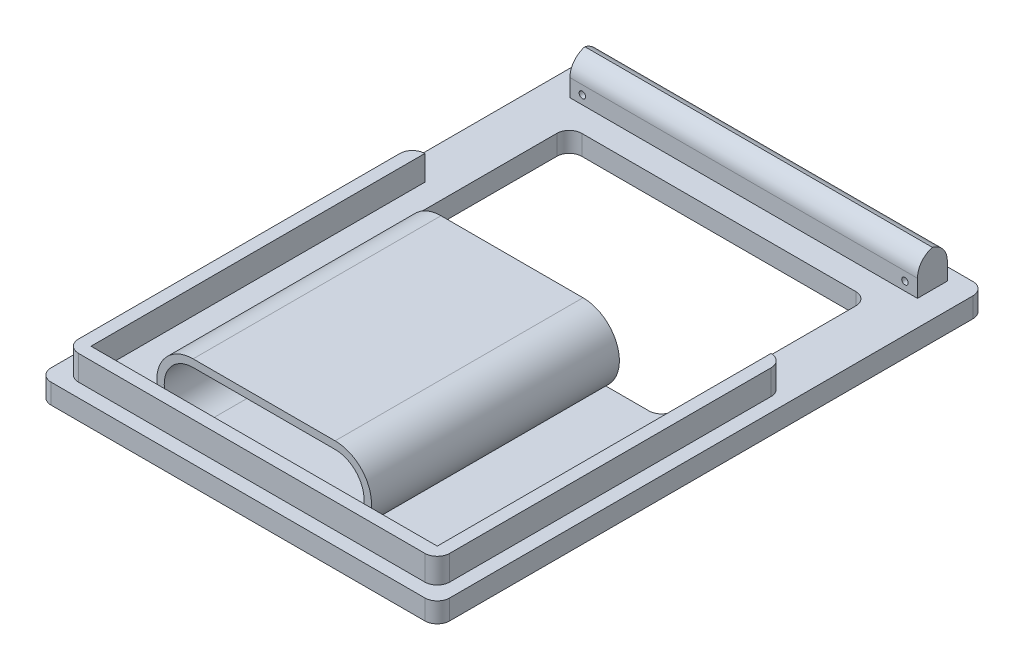
SolidWorks part; units mm, degrees
ref_plane "Front Plane" through (0, 0, 0) normal (0, 0, 1) x (1, 0, 0)
ref_plane "Top Plane" through (0, 0, 0) normal (0, 1, 0) x (1, 0, 0)
ref_plane "Right Plane" through (0, 0, 0) normal (1, 0, 0) x (0, 0, -1)
sketch "Sketch3" plane through (0, 0, 0) normal (0, 1, 0) x (1, 0, 0)
  line L0 (-75, 110) -> (75, 110)
  line L1 (-75, -105) -> (75, -105)
  line L2 (-75, -105) -> (-75, 105)
  line L4 (75, -105) -> (75, 105)
  line L5 (-75, -105) -> (75, 105) construction
  line L6 (-75, 105) -> (75, -105) construction
  line L7 (80, -105) -> (80, 105)
  line L8 (-75, -110) -> (75, -110)
  line L9 (-80, -105) -> (-80, 105)
  line L10 (-80, -110) -> (80, -110) construction
  line L11 (-80, -110) -> (-80, 110) construction
  line L12 (80, -110) -> (80, 110) construction
  line L13 (-80, 110) -> (80, 110) construction
  line L15 (-75, 105) -> (75, 105)
  line L19 (-75, 105) -> (75, 105) construction
  line L20 (-69.75, 105) -> (69.75, 105)
  line L21 (-69.75, 105) -> (-69.75, 93)
  line L22 (-69.75, 93) -> (69.75, 93)
  line L23 (69.75, 105) -> (69.75, 93)
  arc A0 (-75, -110) -> (-80, -105) centre (-75, -105) cw
  arc A1 (80, -105) -> (75, -110) centre (75, -105) cw
  arc A2 (75, 110) -> (80, 105) centre (75, 105) cw
  arc A3 (-75, 110) -> (-80, 105) centre (-75, 105) ccw
  point P0 (0, 0)
  point P5 (0, 93)
  dimension "D4" = 5
  dimension "D1" = 75
  dimension "D2" = 210
  dimension "D5" = 12
  dimension "D6" = 139.5
  dimension "D3" = 5
extrude "Boss-Extrude1" add sketch "Sketch3" along normal blind 8 contours L1 L4 L2 | L0 A3 L9 A0 L8 A1 L7 A2 L4 L1 L2 | L2 L4 | L23 L15 L21 L22 region at (0, 0, -107.2797) region at (0, 0, 5.5564) region at (0, 0, -99)
extrude "Boss-Extrude2" add sketch "Sketch3<7>" along normal blind 15 from surface contours L23 L15 L21 L22 region at (0, 0, -99) starting at face at (0, 8, 0)
sketch "Sketch3<7>" plane through (0, 0, 0) normal (0, 1, 0) x (1, 0, 0) same geometry as "Sketch3"
fillet "Fillet1" radius 8 2 edges at (0, 23, -93) (0, 23, -105)
sketch "Sketch4" plane through (0, 0, 0) normal (0, -1, 0) x (1, 0, 0)
  line L0 (69.75, -93) -> (-69.75, -93) construction
  line L1 (-55, 0) -> (55, 0)
  line L2 (-60, -5) -> (-60, -78)
  line L3 (-55, -83) -> (55, -83)
  line L4 (60, -5) -> (60, -78)
  line L5 (-75, 110) -> (75, 110) construction
  line L6 (80, 105) -> (80, -105) construction
  arc A0 (-55, 0) -> (-60, -5) centre (-55, -5) ccw
  arc A1 (-60, -78) -> (-55, -83) centre (-55, -78) ccw
  arc A2 (55, -83) -> (60, -78) centre (55, -78) ccw
  arc A3 (55, 0) -> (60, -5) centre (55, -5) cw
  point P4 (0, -83)
  point P12 (0, 0)
  dimension "D4" = 5
  dimension "D1" = 10
  dimension "D2" = 110
  dimension "D3" = 20
extrude "Cut-Extrude1" cut sketch "Sketch4" against normal up to next
sketch "Sketch5" plane through (0, 8, 0) normal (0, 1, 0) x (1, 0, 0)
  line L0 (75, -105) -> (75, 105) construction
  line L1 (-75, -105) -> (75, -105) construction
  line L2 (-75, -105) -> (-75, 105) construction
  line L3 (-75, 105) -> (75, 105) construction
  line L4 (75, 110) -> (-75, 110)
  line L5 (80, -105) -> (80, 105)
  line L6 (-75, -110) -> (75, -110)
  line L7 (-80, 105) -> (-80, -105)
  line L8 (75, 110) -> (-75, 110)
  line L9 (80, -105) -> (80, 105)
  line L10 (-75, -110) -> (75, -110)
  line L11 (-80, 105) -> (-80, -105)
  line L12 (69.75, 105) -> (-69.75, 105)
  line L13 (-69.75, 105) -> (-69.75, 93)
  line L14 (-69.75, 93) -> (69.75, 93)
  line L15 (69.75, 93) -> (69.75, 105)
  line L16 (69.75, 105) -> (-69.75, 105)
  line L17 (-69.75, 105) -> (-69.75, 93)
  line L18 (-69.75, 93) -> (69.75, 93)
  line L19 (69.75, 93) -> (69.75, 105)
  line L20 (75, -105) -> (75, 105)
  line L21 (-75, -105) -> (75, -105)
  line L22 (-75, -105) -> (-75, 105)
  line L23 (-75, 105) -> (75, 105)
  line L24 (-75, 35) -> (75, 35)
  line L25 (-69.5, 34.5) -> (-69.5, -99.5)
  line L26 (-69.5, -104.5) -> (69.5, -104.5)
  line L27 (-74.5, -99.5) -> (-74.5, 29.5)
  line L28 (-69.5, 34.5) -> (69.5, 34.5)
  line L29 (74.5, -99.5) -> (74.5, 29.5)
  line L30 (-69.5, -99.5) -> (69.5, -99.5)
  line L31 (69.5, -99.5) -> (69.5, 34.5)
  arc A0 (-74.5, 29.5) -> (-69.5, 34.5) centre (-69.5, 29.5) cw
  arc A1 (69.5, 34.5) -> (74.5, 29.5) centre (69.5, 29.5) cw
  arc A2 (69.5, -104.5) -> (74.5, -99.5) centre (69.5, -99.5) ccw
  arc A3 (-69.5, -104.5) -> (-74.5, -99.5) centre (-69.5, -99.5) cw
  arc A4 (80, 105) -> (75, 110) centre (75, 105) ccw
  arc A5 (75, -110) -> (80, -105) centre (75, -105) ccw
  arc A6 (-80, -105) -> (-75, -110) centre (-75, -105) ccw
  arc A7 (-75, 110) -> (-80, 105) centre (-75, 105) ccw
  arc A8 (80, 105) -> (75, 110) centre (75, 105) ccw
  arc A9 (75, -110) -> (80, -105) centre (75, -105) ccw
  arc A10 (-80, -105) -> (-75, -110) centre (-75, -105) ccw
  arc A11 (-75, 110) -> (-80, 105) centre (-75, 105) ccw
  point P26 (0, -104.5)
  point P40 (0, 0)
  point P41 (54.28, 86.5)
  point P42 (0, -99.5)
  dimension "D7" = 5
  dimension "D3" = 75
  dimension "D4" = 0.5
  dimension "D5" = 0.5
  dimension "D6" = 0.5
  dimension "D8" = 5
  dimension "D9" = 5
  dimension "D1" = 0
  dimension "D2" = 0
extrude "Boss-Extrude3" add sketch "Sketch5" along normal blind 10 contours A3 L26 A2 L29 A1 L31 L30 L25 A0 L27 region at (-71.5377, 8, 32.5)
sketch "Sketch6" plane through (0, 0, -105) normal (0, 0, -1) x (-1, 0, 0)
  line L0 (-69.75, 15) -> (-69.75, 8) construction
  line L1 (0, 0) -> (0, 22.746) construction
  line L2 (-69.75, 22.746) -> (69.75, 22.746) construction
  circle A0 centre (-64.75, 11.5) radius 1.3
  circle A1 centre (64.75, 11.5) radius 1.3
  point P5 (-69.75, 11.5)
  dimension "D1" = 2.6
  dimension "D2" = 5
extrude "Cut-Extrude2" cut sketch "Sketch6" against normal up to next
sketch "Sketch8" plane through (0, 0, 99.5) normal (0, 0, -1) x (-1, 0, 0)
  line L0 (-28.5, 19.5) -> (28.5, 19.5) construction
  line L1 (-28.5, 31) -> (28.5, 31)
  line L2 (-28.5, 8) -> (28.5, 8)
  line L3 (69.5, 8) -> (-69.5, 8) construction
  line L4 (0, 19.5) -> (0, 0) construction
  line L5 (-28.5, 31.1) -> (28.5, 31.1)
  line L6 (-28.5, 7.9) -> (28.5, 7.9)
  line L7 (-28.5, 34.1) -> (28.5, 34.1)
  line L8 (-28.5, 4.9) -> (28.5, 4.9)
  line L9 (-37.495, 8) -> (37.495, 8)
  arc A0 (-28.5, 31) -> (-28.5, 8) centre (-28.5, 19.5) ccw
  arc A1 (28.5, 8) -> (28.5, 31) centre (28.5, 19.5) ccw
  arc A2 (28.5, 7.9) -> (28.5, 31.1) centre (28.5, 19.5) ccw
  arc A3 (-28.5, 31.1) -> (-28.5, 7.9) centre (-28.5, 19.5) ccw
  arc A4 (28.5, 4.9) -> (28.5, 34.1) centre (28.5, 19.5) ccw
  arc A5 (-28.5, 34.1) -> (-28.5, 4.9) centre (-28.5, 19.5) ccw
  point P2 (0, 19.5)
  line M6 (-69.5, 8) -> (69.5, 8)
  line M8 (69.5, 18) -> (-69.5, 18)
  dimension "D2" = 80
  dimension "D1" = 23
  dimension "D3" = 0.1
  dimension "D4" = 3
extrude "Boss-Extrude4" add sketch "Sketch8" along normal up to surface (99.5 mm away) contours L7 A5 A3 L5 A2 A4 M8 | L9 A4 A2 M8 | A5 A3 M8 M6 region at (41.5127, 18.8769, 99.5) region at (38.7612, 12.3911, 99.5) region at (-38.7612, 12.3911, 99.5) up to face at (0, 4, 0)
